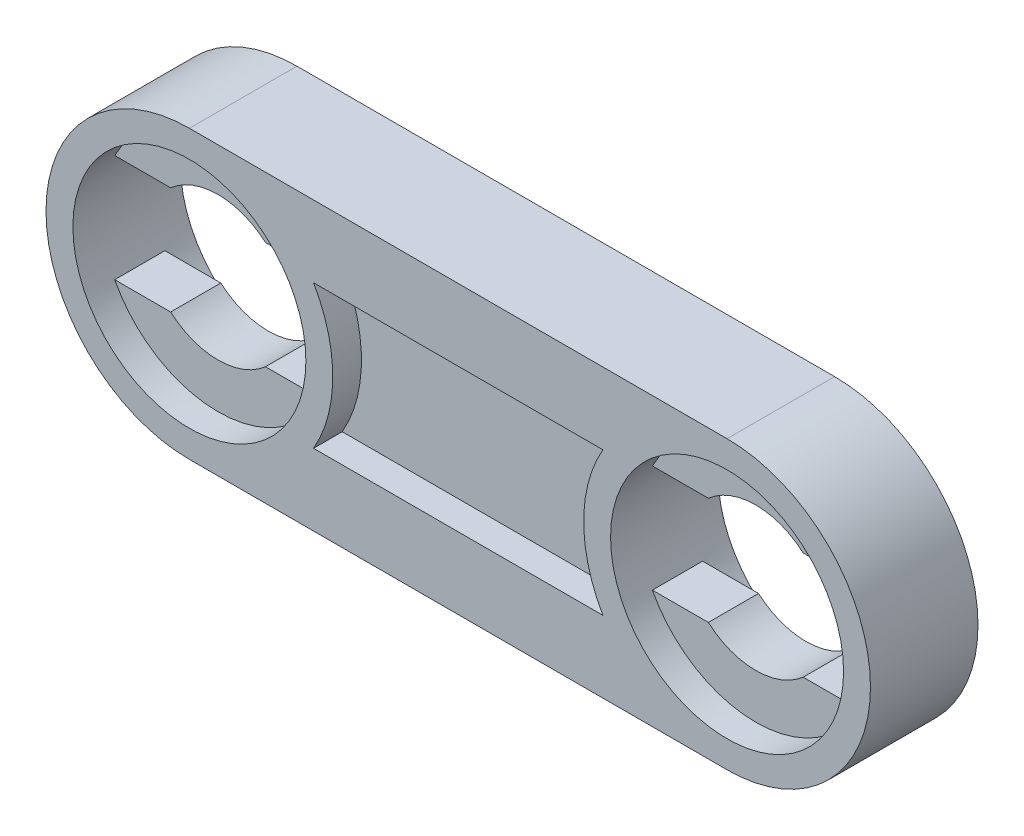
SolidWorks part; units mm, degrees
note: The reader was unsure of these and kept them because the rebuilt part matched: shared geometry of "草图3<2>".
ref_plane "前视基准面" through (0, 0, 0) normal (0, 0, 1) x (1, 0, 0)
ref_plane "上视基准面" through (0, 0, 0) normal (0, 1, 0) x (1, 0, 0)
ref_plane "右视基准面" through (0, 0, 0) normal (1, 0, 0) x (0, 0, -1)
sketch "草图1" plane through (0, 0, 0) normal (0, 0, 1) x (1, 0, 0)
  line L1 (0, 4) -> (15, 4)
  line L3 (0, -4) -> (15, -4)
  arc A0 (0, 4) -> (0, -4) centre (0, 0) ccw
  arc A3 (15, -4) -> (15, 4) centre (15, 0) ccw
extrude "凸台-拉伸1" add sketch "草图1" against normal blind 3
sketch "草图2" plane through (0, 0, 0) normal (0, 0, 1) x (1, 0, 0)
  line L0 (1.3229, -1.5) -> (2.8831, -1.5)
  line L1 (-2.8831, -1.5) -> (-1.3229, -1.5)
  line L2 (1.3229, 1.5) -> (2.8831, 1.5)
  line L3 (-2.8831, 1.5) -> (-1.3229, 1.5)
  arc A0 (1.3229, 1.5) -> (-1.3229, 1.5) centre (0, 0) ccw
  arc A1 (-2.8831, 1.5) -> (-2.8831, -1.5) centre (0, 0) ccw
  arc A3 (2.8831, -1.5) -> (2.8831, 1.5) centre (0, 0) ccw
  arc A4 (-1.3229, -1.5) -> (1.3229, -1.5) centre (0, 0) ccw
extrude "切除-拉伸1" cut sketch "草图2" against normal up to next
sketch "草图3" plane through (0, 0, 0) normal (0, 0, 1) x (1, 0, 0)
  circle A1 centre (0, 0) radius 3.25
extrude "切除-拉伸2" cut sketch "草图3" against normal blind 0.8
extrude "切除-拉伸3" cut sketch "草图3<2>" along normal blind 0.8 from offset 3 offset against normal yes
sketch "草图3<2>" plane through (0, 0, 0) normal (0, 0, 1) x (1, 0, 0) same geometry as "草图3"
ref_plane "基准面1" through (7.5, 0, 0) normal (1, 0, 0) x (0, 0, -1)
mirror "镜向1" about plane through (7.5, 0, 0) normal (1, 0, 0) of "切除-拉伸3", "切除-拉伸2", "切除-拉伸1"
sketch "草图4" plane through (0, 0, 0) normal (0, 0, 1) x (1, 0, 0)
  line L0 (3.4641, 2) -> (11.5359, 2)
  line L2 (3.4641, -2) -> (11.5359, -2)
  arc A0 (3.4641, -2) -> (3.4641, 2) centre (0, 0) ccw
  arc A1 (11.5359, 2) -> (11.5359, -2) centre (15, 0) ccw
extrude "切除-拉伸4" cut sketch "草图4" against normal blind 0.8
sketch "草图5" plane through (0, 0, -3) normal (0, 0, -1) x (-1, 0, 0)
  line L1 (-11, -2) -> (-4, -2)
  line L2 (-11, -2) -> (-11, 2)
  line L3 (-11, 2) -> (-4, 2)
  line L4 (-4, -2) -> (-4, 2)
extrude "切除-拉伸5" cut sketch "草图5" against normal blind 0.8
